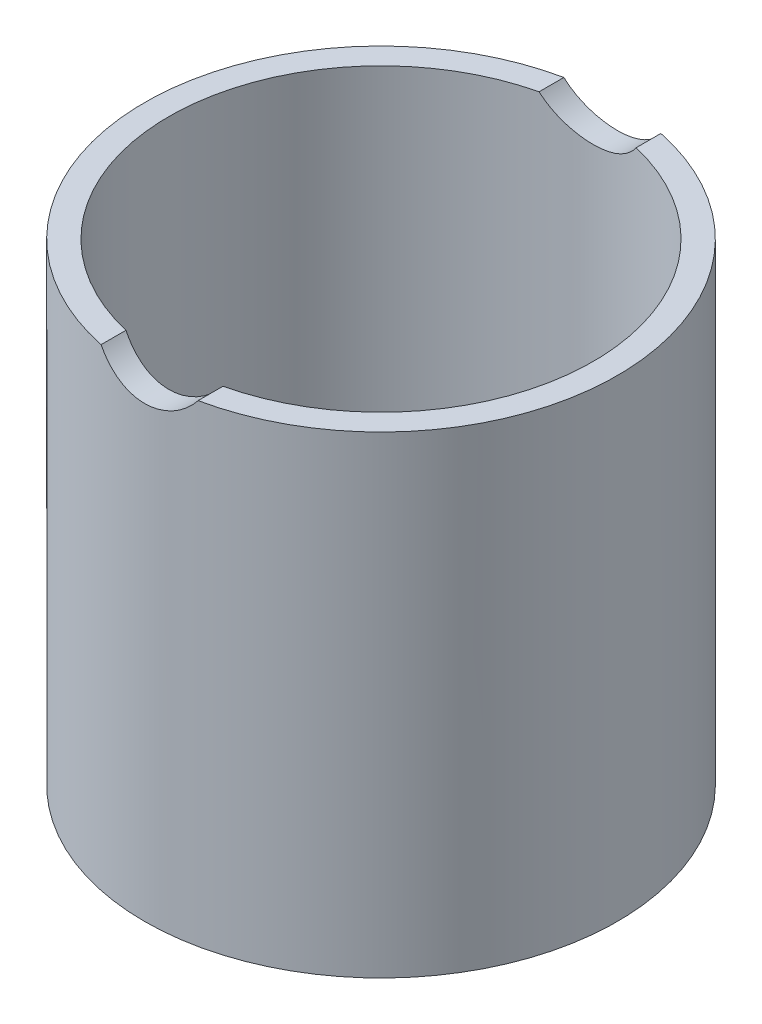
SolidWorks part; units mm, degrees
ref_plane "Front Plane" through (0, 0, 0) normal (0, 0, 1) x (1, 0, 0)
ref_plane "Top Plane" through (0, 0, 0) normal (0, 1, 0) x (1, 0, 0)
ref_plane "Right Plane" through (0, 0, 0) normal (1, 0, 0) x (0, 0, -1)
sketch "Sketch1" plane through (0, 0, 0) normal (0, 1, 0) x (1, 0, 0)
  circle A0 centre (0, 0) radius 19.5
  circle A1 centre (0, 0) radius 17.5
  dimension "D1" = 35
  dimension "D2" = 39
extrude "Boss-Extrude1" add sketch "Sketch1" along normal blind 37
extrude "Boss-Extrude2" add sketch "Sketch1<2>" against normal blind 2 contours A0 A1 | A1 region at (-18.9485, 0, 0) region at (0, 0, 0)
sketch "Sketch1<2>" plane through (0, 0, 0) normal (0, 1, 0) x (1, 0, 0) same geometry as "Sketch1"
sketch "Sketch2" plane through (0, 0, 0) normal (0, 0, 1) x (1, 0, 0)
  circle A0 centre (0, 40) radius 5
  point P2 (0, 35)
  dimension "D2" = 10
  dimension "D1" = 35
extrude "Cut-Extrude1" cut sketch "Sketch2" against normal through all both and the other way through all contours A0
